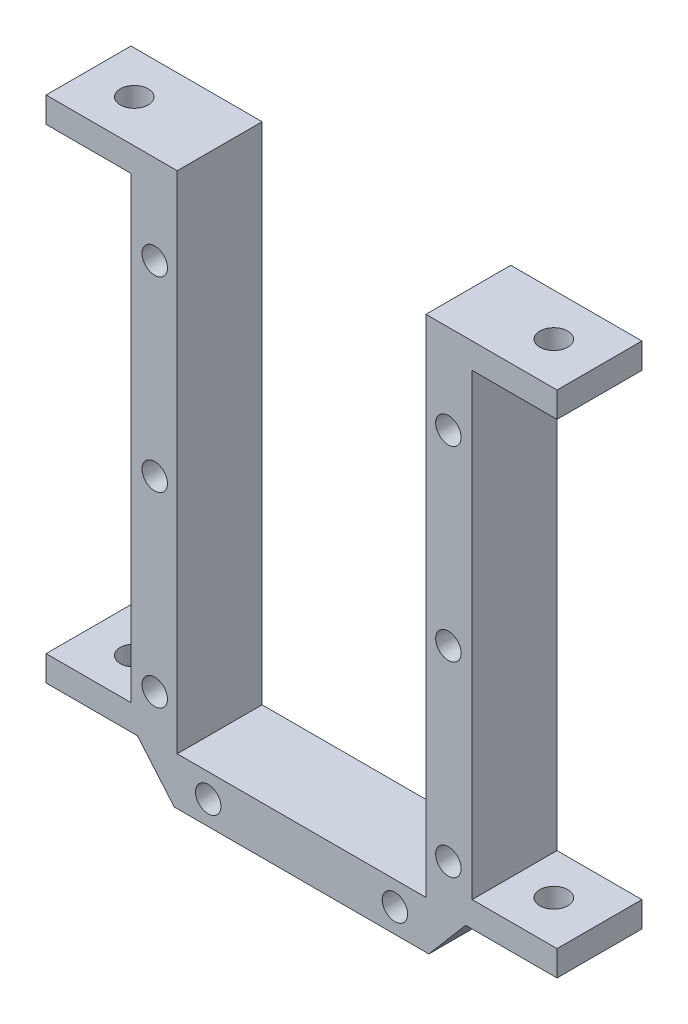
SolidWorks part; units mm, degrees
ref_plane "Front Plane" through (0, 0, 0) normal (0, 0, 1) x (1, 0, 0)
ref_plane "Top Plane" through (0, 0, 0) normal (0, 1, 0) x (1, 0, 0)
ref_plane "Right Plane" through (0, 0, 0) normal (1, 0, 0) x (0, 0, -1)
sketch "Sketch1" plane through (0, 0, 0) normal (0, 0, 1) x (1, 0, 0)
  line L1 (-20.1, 32.55) -> (20.1, 32.55)
  line L2 (-20.1, 32.55) -> (-20.1, -32.55)
  line L3 (-20.1, -32.55) -> (20.1, -32.55)
  line L4 (20.1, 32.55) -> (20.1, -32.55)
  point P0 (0, 0)
  dimension "D1" = 40.2
  dimension "D2" = 65.1
extrude "Boss-Extrude1" add sketch "Sketch1" along normal blind 10
sketch "Sketch2" plane through (0, 0, 10) normal (0, 0, 1) x (1, 0, 0)
  line L0 (0, 32.55) -> (0, -32.55) construction
  line L1 (20.1, 32.55) -> (-20.1, 32.55) construction
  line L2 (-20.1, -32.55) -> (20.1, -32.55) construction
  line L3 (-20.1, 0) -> (20.1, 0) construction
  line L4 (-20.1, 32.55) -> (-20.1, -32.55) construction
  line L5 (20.1, -32.55) -> (20.1, 32.55) construction
  line L6 (-20.1, -27.45) -> (20.1, -27.45) construction
  line L7 (15, -32.55) -> (19.335, -27.45)
  line L8 (19.335, -27.45) -> (15, -32.55) construction
  line L9 (19.335, -27.45) -> (20.1, -27.45)
  line L22 (20.1, -27.45) -> (20.1, -32.55)
  line L23 (20.1, -32.55) -> (15, -32.55)
  line L24 (-20.1, -27.45) -> (-20.1, -32.55)
  line L25 (-19.335, -27.45) -> (-20.1, -27.45)
  line L26 (-15, -32.55) -> (-19.335, -27.45)
  line L27 (-20.1, -32.55) -> (-15, -32.55)
  point P12 (0, -27.45)
  point P13 (-19.335, -27.45)
  point P17 (0, -27.45)
  point P18 (19.335, -27.45)
  dimension "D1" = 60
extrude "Cut-Extrude1" cut sketch "Sketch2" against normal blind 10
sketch "Sketch4" plane through (0, 0, 10) normal (0, 0, 1) x (1, 0, 0)
  line L0 (0, 32.55) -> (0, -32.55) construction
  line L1 (20.1, 32.55) -> (-20.1, 32.55) construction
  line L2 (-15, -32.55) -> (15, -32.55) construction
  line L3 (-20.1, 2.55) -> (20.1, 2.55) construction
  line L4 (-20.1, 32.55) -> (-20.1, -27.45) construction
  line L5 (20.1, -27.45) -> (20.1, 32.55) construction
  line L6 (14.65, -26.95) -> (-14.65, -26.95) construction
  line L7 (-14.65, -26.95) -> (-14.65, 32.55) construction
  line L8 (14.65, -26.95) -> (14.65, 32.55) construction
  line L9 (-14.65, 32.55) -> (-14.65, -26.95)
  line L10 (-14.65, -26.95) -> (14.65, -26.95)
  line L11 (14.65, -26.95) -> (14.65, 32.55)
  line L12 (14.65, 32.55) -> (-14.65, 32.55)
  point P12 (0, -26.95)
  point P16 (0, -26.95)
  dimension "D1" = 5.6
  dimension "D2" = 29.3
extrude "Cut-Extrude2" cut sketch "Sketch4" against normal blind 10
sketch "Sketch5" plane through (0, 0, 10) normal (0, 0, 1) x (1, 0, 0)
  line L0 (-14.65, 32.55) -> (14.65, 32.55) construction
  line L1 (0, 32.55) -> (0, -32.55) construction
  line L2 (-15, -32.55) -> (15, -32.55) construction
  line L3 (-15, -32.55) -> (15, -32.55) construction
  line L6 (-20.1, 32.55) -> (-20.1, -27.45) construction
  circle A0 centre (-17.3, 22.05) radius 1.5
  circle A1 centre (-17.3, 0.05) radius 1.5
  circle A2 centre (-17.3, -21.95) radius 1.5
  circle A3 centre (-11, -29.75) radius 1.5
  circle A4 centre (11, -29.75) radius 1.5
  circle A5 centre (17.3, -21.95) radius 1.5
  circle A6 centre (17.3, 0.05) radius 1.5
  circle A7 centre (17.3, 22.05) radius 1.5
  point P8 (-17.3, 22.05)
  point P9 (-17.3, 0.05)
  point P10 (-17.3, -21.95)
  point P11 (-11, -29.75)
  point P22 (11, -29.75)
  point P25 (17.3, -21.95)
  point P28 (17.3, 0.05)
  point P31 (17.3, 22.05)
  dimension "D6" = 3
  dimension "D7" = 3
  dimension "D8" = 3
  dimension "D9" = 3
  dimension "D1" = 10.6
  dimension "D2" = 32.6
  dimension "D3" = 54.6
  dimension "D4" = 2.8
  dimension "D5" = 9.1
  dimension "D10" = 17.3
  dimension "D11" = 17.3
  dimension "D12" = 17.3
extrude "Cut-Extrude3" cut sketch "Sketch5" against normal blind 10
sketch "Sketch6" plane through (0, 0, 10) normal (0, 0, 1) x (1, 0, 0)
  line L0 (-14.65, 32.55) -> (14.65, 32.55) construction
  line L1 (0, 32.55) -> (0, -32.55) construction
  line L2 (-15, -32.55) -> (15, -32.55) construction
  line L3 (-20.1, 2.55) -> (20.1, 2.55) construction
  line L4 (-20.1, 32.55) -> (-20.1, -27.45) construction
  line L5 (20.1, -27.45) -> (20.1, 32.55) construction
sketch "Sketch7" plane through (20.1, 0, 0) normal (1, 0, 0) x (0, 0, -1)
  line L0 (0, 2.55) -> (-10, 2.55) construction
  line L1 (-10, 32.55) -> (-10, -32.55) construction
  line L2 (0, -27.45) -> (0, 32.55) construction
  line L3 (0, 29.55) -> (-10, 29.55)
  line L4 (-10, 29.55) -> (-10, 32.55)
  line L5 (-10, 32.55) -> (0, 32.55)
  line L6 (0, 32.55) -> (0, 29.55)
  line L7 (-10, -27.45) -> (-10, 32.55) construction
  line L8 (-10, -27.45) -> (0, -27.45)
  line L9 (-10, -24.45) -> (-10, -27.45)
  line L10 (0, -24.45) -> (-10, -24.45)
  line L11 (0, -27.45) -> (0, -24.45)
  point P5 (0, 29.55)
  dimension "D1" = 3
extrude "Boss-Extrude2" add sketch "Sketch7" along normal blind 10
sketch "Sketch8" plane through (-20.1, 0, 0) normal (-1, 0, 0) x (0, 0, 1)
  line L0 (0, 2.55) -> (10, 2.55) construction
  line L1 (0, 32.55) -> (0, -27.45) construction
  line L2 (10, 32.55) -> (10, -32.55) construction
  line L3 (0, 29.55) -> (10, 29.55)
  line L4 (10, 29.55) -> (10, 32.55)
  line L5 (10, 32.55) -> (0, 32.55)
  line L6 (0, 32.55) -> (0, 29.55)
  line L7 (10, -27.45) -> (0, -27.45)
  line L8 (10, -24.45) -> (10, -27.45)
  line L9 (0, -24.45) -> (10, -24.45)
  line L10 (0, -27.45) -> (0, -24.45)
  point P6 (0, 29.55)
  dimension "D1" = 3
extrude "Boss-Extrude3" add sketch "Sketch8" along normal blind 10
sketch "Sketch9" plane through (0, -27.45, 0) normal (0, -1, 0) x (-1, 0, 0)
  line L0 (24.7175, -10) -> (24.7175, 0) construction
  line L1 (19.335, -10) -> (30.1, -10) construction
  line L2 (19.335, 0) -> (30.1, 0) construction
  line L3 (30.1, -5) -> (19.335, -5) construction
  line L4 (30.1, 0) -> (30.1, -10) construction
  line L5 (19.335, 0) -> (19.335, -10) construction
  circle A0 centre (24.7175, -5) radius 1.65
  dimension "D1" = 3.3
extrude "Cut-Extrude4" cut sketch "Sketch9" against normal through all
sketch "Sketch10" plane through (0, -27.45, 0) normal (0, -1, 0) x (-1, 0, 0)
  line L0 (-24.7175, -10) -> (-24.7175, 0) construction
  line L1 (-30.1, -10) -> (-19.335, -10) construction
  line L2 (-30.1, 0) -> (-19.335, 0) construction
  line L3 (-19.335, -5) -> (-30.1, -5) construction
  line L4 (-19.335, 0) -> (-19.335, -10) construction
  line L5 (-30.1, -10) -> (-30.1, 0) construction
  circle A0 centre (-24.7175, -5) radius 1.65
  dimension "D1" = 3.3
extrude "Cut-Extrude5" cut sketch "Sketch10" against normal through all
